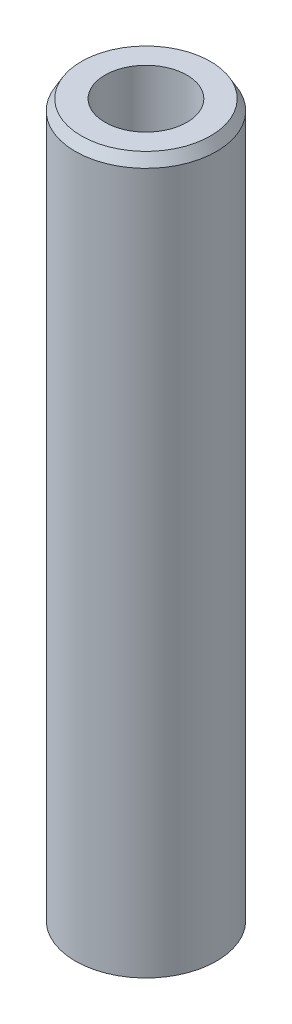
SolidWorks part; units mm, degrees
ref_plane "Front Plane" through (0, 0, 0) normal (0, 0, 1) x (1, 0, 0)
ref_plane "Top Plane" through (0, 0, 0) normal (0, 1, 0) x (1, 0, 0)
ref_plane "Right Plane" through (0, 0, 0) normal (1, 0, 0) x (0, 0, -1)
sketch "Sketch1" plane through (0, 0, 0) normal (0, 1, 0) x (1, 0, 0)
  circle A0 centre (0, 0) radius 22.5
  dimension "SHAFT_OD" = 45
extrude "Boss-Extrude1" add sketch "Sketch1" along normal blind 228.8127
sketch "Sketch2" plane through (0, 0, 0) normal (0, 1, 0) x (1, 0, 0)
  circle A0 centre (0, 0) radius 13.0582
  dimension "BORE_D" = 26.1164
extrude "Cut-Extrude1" cut sketch "Sketch2" along normal through all
chamfer "Chamfer1" distance 3.3294 angle 30 2 edges at (0, 228.8127, 22.5) (0, 0, 22.5) first distance on face at (0, 228.8127, 22.5) first distance on face at (0, 0, 13.0582)
